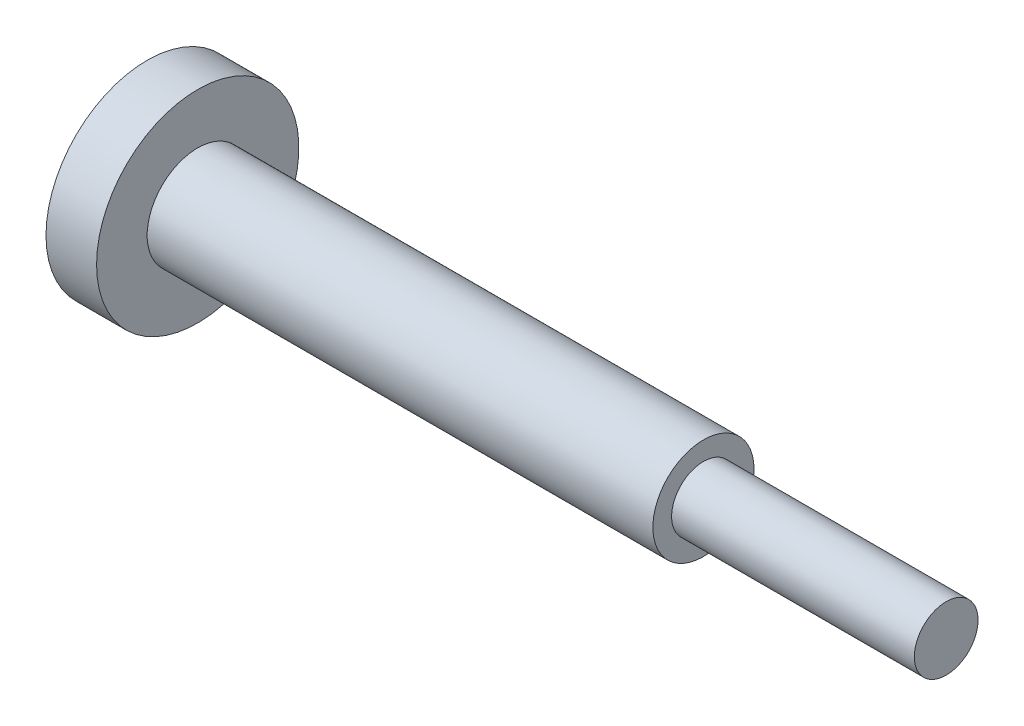
SolidWorks part; units mm, degrees
material "Plain Carbon Steel"
ref_plane "Front Plane" through (0, 0, 0) normal (0, 0, 1) x (1, 0, 0)
ref_plane "Top Plane" through (0, 0, 0) normal (0, 1, 0) x (1, 0, 0)
ref_plane "Right Plane" through (0, 0, 0) normal (1, 0, 0) x (0, 0, -1)
sketch "Sketch1" plane through (0, 0, 0) normal (1, 0, 0) x (0, 0, -1)
  circle A0 centre (0, 0) radius 3.175
  circle A1 centre (0, 0) radius 2
  dimension "D1" = 6.35
  dimension "D2" = 4
extrude "Boss-Extrude1" add sketch "Sketch1" along normal blind 15.24 contours A0 | A1 region at (0, 0, 0)
extrude "Boss-Extrude2" add sketch "Sketch1<3>" against normal blind 31.75 contours A0 | A1 region at (0, 0, 3.0852) region at (0, 0, 0)
sketch "Sketch1<3>" plane through (0, 0, 0) normal (1, 0, 0) x (0, 0, -1) same geometry as "Sketch1"
sketch "Sketch2" plane through (-31.75, 0, 0) normal (-1, 0, 0) x (0, 0, 1)
  circle A0 centre (0, 0) radius 6.35
  dimension "D1" = 12.7
extrude "Boss-Extrude3" add sketch "Sketch2" along normal blind 3.175
